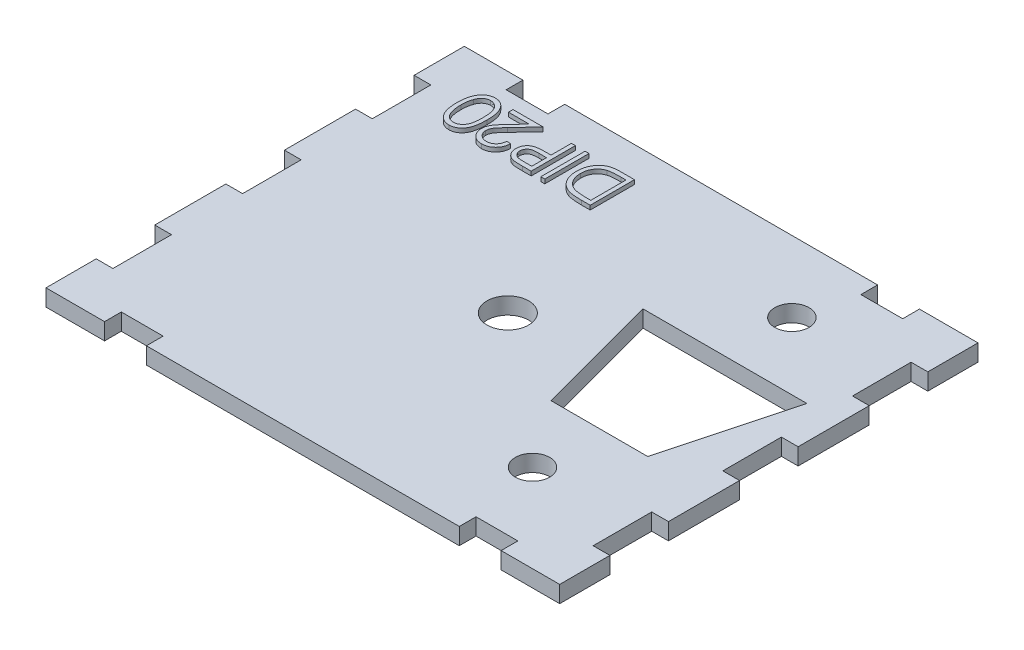
SolidWorks part; units mm, degrees
ref_plane "Front Plane" through (0, 0, 0) normal (0, 0, 1) x (1, 0, 0)
ref_plane "Top Plane" through (0, 0, 0) normal (0, 1, 0) x (1, 0, 0)
ref_plane "Right Plane" through (0, 0, 0) normal (1, 0, 0) x (0, 0, -1)
sketch "Sketch2" plane through (0, 0, 0) normal (0, 1, 0) x (1, 0, 0)
  line L1 (-50, 25) -> (50, 25)
  line L2 (-50, 25) -> (-50, -25)
  line L3 (-50, -25) -> (50, -25)
  line L4 (50, 25) -> (50, -25)
  line L5 (-50, 25) -> (50, -25) construction
  line L6 (-50, -25) -> (50, 25) construction
  point P0 (0, 0)
  dimension "D1" = 100
  dimension "D2" = 50
extrude "Boss-Extrude1" add sketch "Sketch2" along normal blind 2
sketch "Sketch12" plane through (0, 2, 0) normal (0, 1, 0) x (1, 0, 0)
  line L0 (-50, -25) -> (50, -25) construction
  line L1 (-40.2, -25) -> (-50, -25)
  line L2 (-40.2, -25) -> (-40.2, 25)
  line L3 (-40.2, 25) -> (-50, 25)
  line L4 (-50, -25) -> (-50, 25)
  line L5 (-50, -25) -> (50, -25) construction
  line L6 (41.2, -25) -> (50, -25)
  line L7 (41.2, -25) -> (41.2, 25)
  line L8 (41.2, 25) -> (50, 25)
  line L9 (50, -25) -> (50, 25)
extrude "Cut-Extrude8" cut sketch "Sketch12" against normal blind 6
sketch "Sketch13" plane through (0, 2, 0) normal (0, 1, 0) x (1, 0, 0)
  line L1 (-28.2, 19) -> (-30.2, 19)
  line L2 (-28.2, 19) -> (-28.2, 12)
  line L3 (-28.2, 12) -> (-30.2, 12)
  line L4 (-30.2, 19) -> (-30.2, 12)
  line L5 (-28.2, 3.5) -> (-30.2, 3.5)
  line L6 (-28.2, 3.5) -> (-28.2, -3.5)
  line L7 (-28.2, -3.5) -> (-30.2, -3.5)
  line L8 (-30.2, 3.5) -> (-30.2, -3.5)
  line L9 (-28.2, -12) -> (-30.2, -12)
  line L10 (-28.2, -12) -> (-28.2, -19)
  line L11 (-28.2, -19) -> (-30.2, -19)
  line L12 (-30.2, -12) -> (-30.2, -19)
  line L13 (29.2, 19) -> (31.2, 19)
  line L14 (29.2, 19) -> (29.2, 12)
  line L15 (29.2, 12) -> (31.2, 12)
  line L16 (31.2, 19) -> (31.2, 12)
  line L17 (29.2, 3.5) -> (31.2, 3.5)
  line L18 (29.2, 3.5) -> (29.2, -3.5)
  line L19 (29.2, -3.5) -> (31.2, -3.5)
  line L20 (31.2, 3.5) -> (31.2, -3.5)
  line L21 (29.2, -12) -> (31.2, -12)
  line L22 (29.2, -12) -> (29.2, -19)
  line L23 (29.2, -19) -> (31.2, -19)
  line L24 (31.2, -12) -> (31.2, -19)
  line L25 (-40.2, -25) -> (41.2, -25) construction
  line L26 (-23.2, 25) -> (-18.2, 25)
  line L27 (41.2, 25) -> (-40.2, 25) construction
  line L28 (-40.2, -25) -> (41.2, -25) construction
  line L29 (41.2, 25) -> (-40.2, 25) construction
  line L30 (-40.2, -25) -> (41.2, -25) construction
  line L31 (41.2, 25) -> (31.2, 25)
  line L32 (41.2, 25) -> (41.2, -25)
  line L33 (41.2, -25) -> (31.2, -25)
  line L34 (31.2, 25) -> (31.2, -25)
  line L35 (41.2, 25) -> (-40.2, 25) construction
  line L36 (-40.2, -25) -> (-30.2, -25)
  line L37 (-40.2, -25) -> (-40.2, 25)
  line L38 (-40.2, 25) -> (-30.2, 25)
  line L39 (-30.2, -25) -> (-30.2, 25)
  line L40 (-23.2, 25) -> (-23.2, 23)
  line L41 (-23.2, 23) -> (-18.2, 23)
  line L42 (-18.2, 25) -> (-18.2, 23)
  line L43 (-23.2, -25) -> (-18.2, -25)
  line L44 (-23.2, -25) -> (-23.2, -23)
  line L45 (-23.2, -23) -> (-18.2, -23)
  line L46 (-18.2, -25) -> (-18.2, -23)
  line L47 (24.2, -25) -> (19.2, -25)
  line L48 (24.2, -25) -> (24.2, -23)
  line L49 (24.2, -23) -> (19.2, -23)
  line L50 (19.2, -25) -> (19.2, -23)
  line L51 (24.2, 25) -> (19.2, 25)
  line L52 (24.2, 25) -> (24.2, 23)
  line L53 (24.2, 23) -> (19.2, 23)
  line L54 (19.2, 25) -> (19.2, 23)
  point P24 (29.2, 0)
  point P30 (30.2, 3.5)
  line M32 (41.2, -25) -> (41.2, 25)
  line M41 (41.2, 25) -> (-40.2, 25)
  line M42 (-40.2, 25) -> (-40.2, -25)
  line M47 (-40.2, -25) -> (41.2, -25)
  dimension "D1" = 2
  dimension "D2" = 2
  dimension "D3" = 2
  dimension "D4" = 2
  dimension "D5" = 2
  dimension "D6" = 2
  dimension "D7" = 57.4
  dimension "D8" = 57.4
  dimension "D9" = 57.4
  dimension "D10" = 7
  dimension "D11" = 7
  dimension "D12" = 7
  dimension "D13" = 7
  dimension "D14" = 7
  dimension "D15" = 7
  dimension "D16" = 5
  dimension "D17" = 2
  dimension "D18" = 5
  dimension "D19" = 6
  dimension "D20" = 8.5
  dimension "D21" = 8.5
  dimension "D22" = 6
  dimension "D23" = 6
  dimension "D24" = 8.5
  dimension "D25" = 8.5
  dimension "D26" = 6
  dimension "D27" = 5
  dimension "D28" = 5
  dimension "D29" = 2
  dimension "D30" = 2
  dimension "D31" = 5
  dimension "D32" = 5
  dimension "D33" = 5
  dimension "D34" = 5
  dimension "D35" = 2
extrude "Cut-Extrude10" cut sketch "Sketch13" against normal blind 6 contours L5 L8 L7 L6 | L39 L12 L8 L4 M47 M41 M42 | L1 L4 L3 L2 | L50 L48 L49 M47 | L24 L21 L22 L23 | L20 L17 L18 L19 | L16 L13 L14 L15 | L54 L53 L52 M41 | L9 L12 L11 L10 | L34 L16 L20 L24 M41 M47 M32 | L26 L42 L41 L40 | L45 L46 L43 L44 region at (-29.2, 2, -15.5) region at (-35.2, 2, 0) region at (-29.2, 2, 0) region at (-29.2, 2, 15.5) region at (21.7, 2, -24) region at (36.2, 2, 0) region at (21.7, 2, 24) region at (30.2, 2, -15.5) region at (30.2, 2, 0) region at (30.2, 2, 15.5)
sketch "Sketch15" plane through (0, 0, 0) normal (0, -1, 0) x (1, 0, 0)
  line L0 (24.2, 23) -> (19.2, 23) construction
  line L16 (20.7242, -7.5) -> (20.7242, -8.5)
  line L17 (20.7242, -7.5) -> (25.936, -7.5)
  line L18 (25.936, -7.5) -> (22.4527, 5.5)
  line L19 (22.4527, 5.5) -> (12.4527, 5.5)
  line L20 (12.4527, 5.5) -> (8.9693, -7.5)
  line L21 (8.9693, -7.5) -> (14.1811, -7.5)
  line L22 (14.1811, -7.5) -> (14.1811, -8.5)
  line L23 (14.1811, -8.5) -> (7.6661, -8.5)
  line L24 (7.6661, -8.5) -> (11.6853, 6.5)
  line L25 (11.6853, 6.5) -> (23.22, 6.5)
  line L26 (23.22, 6.5) -> (27.2392, -8.5)
  line L27 (27.2392, -8.5) -> (20.7242, -8.5)
  line L28 (20.7242, -8.5) -> (14.1811, -8.5)
  line L29 (14.1811, -7.5) -> (20.7242, -7.5)
  line L31 (29.2, 12) -> (29.2, 19) construction
  dimension "D4" = 16.5
  dimension "D18" = 11.5347
  dimension "D19" = 15.5291
  dimension "D20" = 15.5291
  dimension "D21" = 13.4586
  dimension "D22" = 13.4586
  dimension "D23" = 10
  dimension "D24" = 5.2118
  dimension "D25" = 5.2118
  dimension "D26" = 6.515
  dimension "D27" = 6.515
  dimension "D28" = 1
  dimension "D29" = 105
  dimension "D30" = 105
  dimension "D31" = 75
  dimension "D32" = 75
  dimension "D33" = 5.98
  dimension "D34" = 1
extrude "Cut-Extrude13" cut sketch "Sketch15" against normal blind 10 contours L21 L29 L17 L18 L19 L20 | L27 L26 L25 L24 L23 L22 L21 L20 L19 L18 L17 L16 | L29 L22 L28 L16 region at (23.3301, 0, -7.7466) region at (17.4527, 0, -1.5597) region at (17.4527, 0, -8)
sketch "Sketch16" plane through (0, 0, 0) normal (0, -1, 0) x (-1, 0, 0)
  circle A0 centre (0, 0) radius 2.5
  dimension "D1" = 5
extrude "Cut-Extrude14" cut sketch "Sketch16" against normal blind 10 contours A0
sketch "Sketch17" plane through (0, 0, 0) normal (0, -1, 0) x (-1, 0, 0)
  line L2 (-27.2392, 8.5) -> (-7.6661, 8.5) construction
  line L4 (-11.6853, -6.5) -> (-23.22, -6.5) construction
  circle A0 centre (-17.4527, -14.5) radius 2.05
  circle A1 centre (-17.4527, 16.5) radius 2.05
  dimension "D1" = 4.1
  dimension "D2" = 4.1
  dimension "D3" = 8
  dimension "D4" = 9.7866
  dimension "D5" = 9.7866
  dimension "D6" = 5.7673
  dimension "D7" = 5.7673
  dimension "D8" = 8
extrude "Cut-Extrude15" cut sketch "Sketch17" against normal blind 3.5
sketch "Sketch22" plane through (0, 2, 0) normal (0, 1, 0) x (1, 0, 0)
  line L0 (-24.5837, 20.8621) -> (9.284, 20.8621) construction
  text T0 "DIP20" font "Century Gothic" height in points 20
extrude "Boss-Extrude4" add sketch "Sketch22" along normal blind 0.5
